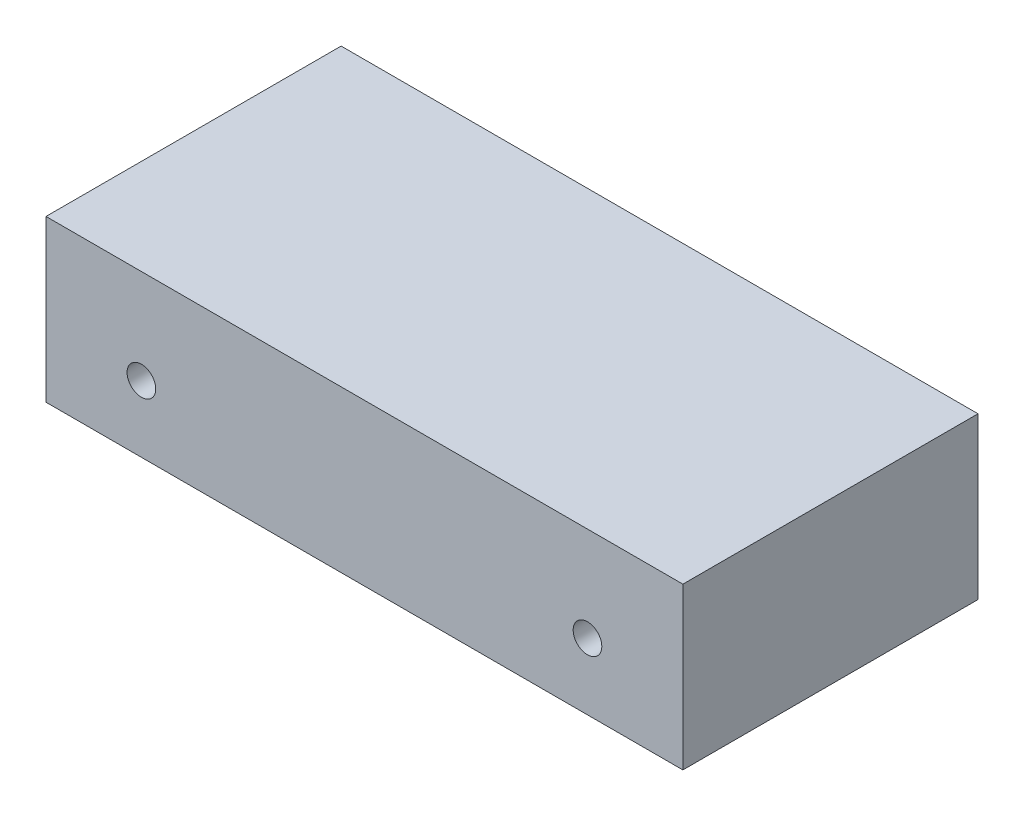
SolidWorks part; units mm, degrees
material "Custom Plastic"
ref_plane "X-Y Datum" through (0, 0, 0) normal (0, 0, 1) x (1, 0, 0)
ref_plane "X-Z Datum" through (0, 0, 0) normal (0, 1, 0) x (1, 0, 0)
ref_plane "Y-Z Datum" through (0, 0, 0) normal (1, 0, 0) x (0, 0, -1)
sketch "Sketch1" plane through (0, 0, 0) normal (0, 0, 1) x (1, 0, 0)
  line L1 (-155.321, 39.243) -> (155.321, 39.243)
  line L2 (-155.321, 39.243) -> (-155.321, -39.243)
  line L3 (-155.321, -39.243) -> (155.321, -39.243)
  line L4 (155.321, 39.243) -> (155.321, -39.243)
  line L5 (-155.321, 39.243) -> (155.321, -39.243) construction
  line L6 (-155.321, -39.243) -> (155.321, 39.243) construction
  point P0 (0, 0)
  dimension "D1" = 310.642
  dimension "D2" = 78.486
extrude "Boss-Extrude1" add sketch "Sketch1" along normal blind 143.9418
sketch "Sketch2" plane through (0, 0, 143.9418) normal (0, 0, 1) x (1, 0, 0)
  line L0 (-155.321, -39.243) -> (155.321, -39.243) construction
  line L1 (-155.321, 39.243) -> (-155.321, -39.243) construction
  circle A0 centre (-108.7882, -6.8834) radius 6.985
  circle A1 centre (108.7882, -6.8834) radius 6.985
  point P8 (0, 0)
  dimension "D3" = 13.97
  dimension "D1" = 32.3596
  dimension "D2" = 46.5328
  dimension "D4" = 217.5764
extrude "Cut-Extrude1" cut sketch "Sketch2" against normal blind 25.4
